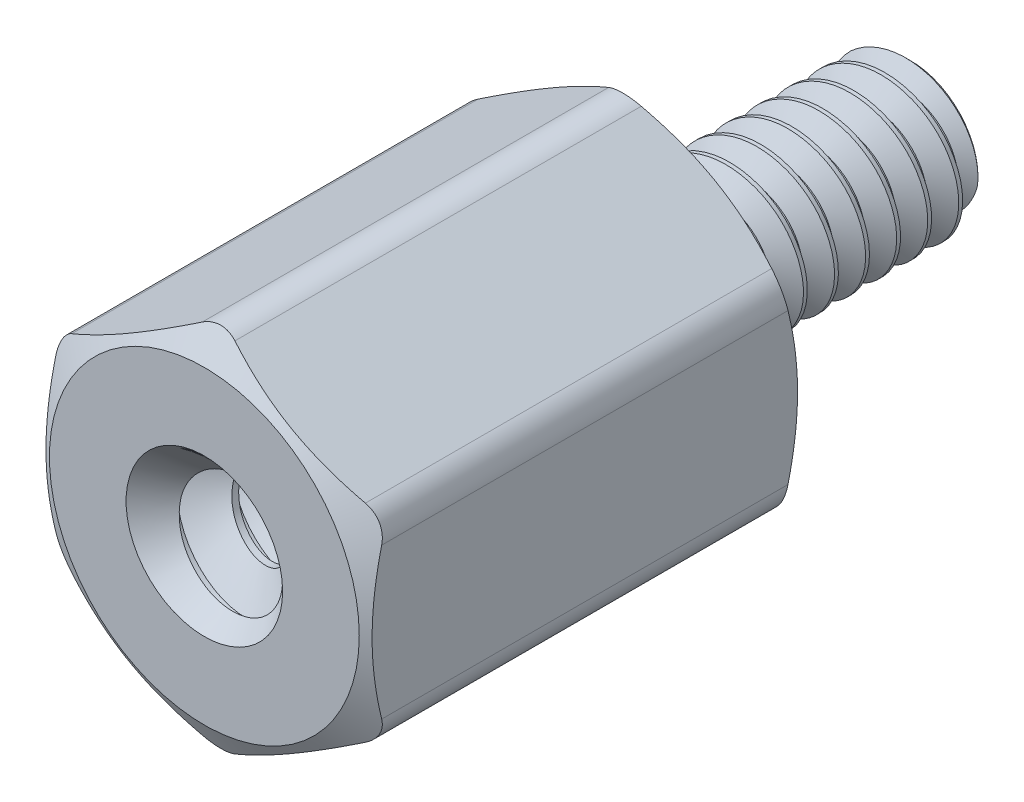
SolidWorks part; units mm, degrees
material "Alloy Steel"
ref_plane "Front Plane" through (0, 0, 0) normal (0, 0, 1) x (1, 0, 0)
ref_plane "Top Plane" through (0, 0, 0) normal (0, 1, 0) x (1, 0, 0)
ref_plane "Right Plane" through (0, 0, 0) normal (1, 0, 0) x (0, 0, -1)
sketch "Sketch1" plane through (0, 0, 0) normal (0, 0, 1) x (1, 0, 0)
  line L1 (2.3813, 1.3748) -> (0, 2.7496)
  line L2 (0, 2.7496) -> (-2.3812, 1.3748)
  line L3 (-2.3812, 1.3748) -> (-2.3812, -1.3748)
  line L4 (-2.3812, -1.3748) -> (0, -2.7496)
  line L5 (0, -2.7496) -> (2.3813, -1.3748)
  line L6 (2.3813, -1.3748) -> (2.3813, 1.3748)
  circle A0 centre (0, 0) radius 2.3812 construction
  point P10 (0, -2.3812)
  dimension "Hex Size" = 4.7625
sketch "Sketch2" plane through (0, 0, 0) normal (1, 0, 0) x (0, 0, -1)
  line L0 (3.9688, 0) -> (-6.35, 0) construction
  line L2 (0, 1.0922) -> (0, -1.0922) construction
  line L3 (-1.5748, 1.0922) -> (-1.5748, -1.0922) construction
  line L4 (-7.0941, 1.1781) -> (-6.6973, 0.4907) construction
  line L5 (-6.6973, 0.4907) -> (-6.3004, 1.1781) construction
  line L6 (-6.3004, 1.1781) -> (-7.0941, 1.1781) construction
  line L7 (-7.0445, 1.0922) -> (-6.35, 1.0922) construction
  line L8 (-6.7469, 0.5766) -> (-6.6477, 0.5766) construction
  line L9 (-6.6973, 0.5766) -> (-6.6973, 0.4907) construction
  line L10 (-6.6973, 1.0922) -> (-6.6973, 1.1781) construction
  line L11 (3.9404, 1.1413) -> (4.394, 1.1413) construction
  line L12 (4.394, 1.1413) -> (4.1672, 0.7485) construction
  line L13 (4.1672, 0.7485) -> (3.9404, 1.1413) construction
  line L14 (3.9688, 1.0922) -> (4.3656, 1.0922) construction
  line L15 (4.1388, 0.7976) -> (4.1955, 0.7976) construction
  line L16 (4.1672, 0.7976) -> (4.1672, 0.7485) construction
  line L17 (4.1672, 1.0922) -> (4.1672, 1.1413) construction
  line L18 (0, 2.7496) -> (-6.35, 2.7496) construction
  point P6 (0, 0)
  point P9 (-1.5748, 0)
  dimension "Length" = 6.35
sketch "Sketch3" plane through (0, 0, 0) normal (1, 0, 0) x (0, 0, -1)
  line L0 (-1.5748, 0) -> (3.9688, 0)
  line L1 (-1.5748, 1.0922) -> (-1.5748, -1.0922) construction
  line L2 (3.9688, 0) -> (3.9688, 0.9788)
  line L3 (3.9688, 0.9788) -> (3.8554, 1.0922)
  line L4 (3.8554, 1.0922) -> (0.6463, 1.0922)
  line L5 (0.6463, 1.0922) -> (0.4763, 0.7976)
  line L6 (-1.5748, 0) -> (-1.5748, 0.9788)
  line L7 (-1.5748, 0.9788) -> (-1.6882, 1.0922)
  line L8 (-1.6882, 1.0922) -> (-6.2366, 1.0922)
  line L9 (-6.2366, 1.0922) -> (-6.35, 1.2056)
  line L10 (3.8554, 0) -> (3.8554, -1.0922) construction
  line L11 (-6.35, 1.2056) -> (-6.35, 2.3812)
  line L12 (-6.35, 2.3812) -> (0, 2.3812)
  line L14 (0.4763, 0.7976) -> (0.1134, 0.7976)
  line L15 (0, 0.911) -> (0, 2.3812)
  arc A0 (0, 0.911) -> (0.1134, 0.7976) centre (0.1134, 0.911) ccw
  point P5 (-6.35, -2.3812)
  point P8 (-4.3656, -1.0922)
  point P9 (2.8348, -1.0922)
  point P27 (0, 0.7976)
  dimension "D4" = 0.1134
  dimension "D2" = 0.1134
  dimension "D1" = 45
  dimension "D6" = 1.1339
  dimension "D7" = 60
  dimension "D3" = 1.9844
  dimension "D5" = 0.4762
revolve "Revolve1" add sketch "Sketch3" angle 360 about L0 region at (0, 1.2337, 1.3349)
sketch "Sketch4" plane through (0, 0, 6.35) normal (0, 0, 1) x (1, 0, 0)
  line L0 (0, 2.3812) -> (0, 1.0922) construction
  line L1 (-2.3812, 1.3748) -> (-2.3812, -1.3748)
  line L2 (-2.3812, -1.3748) -> (0, -2.7496)
  line L3 (0, -2.7496) -> (2.3812, -1.3748)
  line L4 (2.3812, -1.3748) -> (2.3812, 1.3748)
  line L5 (2.3812, 1.3748) -> (0, 2.7496)
  line L6 (0, 2.7496) -> (-2.3812, 1.3748)
  circle A0 centre (0, 0) radius 2.3812 construction
  circle A1 centre (0, 0) radius 1.7367
  circle A2 centre (0, 0) radius 2.3812 construction
  point P16 (0, 1.7367)
extrude "Boss-Extrude1" add sketch "Sketch4" against normal up to surface (6.35 mm away) up to face at (0, 2.3812, 0)
sketch "Sketch5" plane through (0, 0, 6.35) normal (0, 0, 1) x (1, 0, 0)
  line L0 (-0.6265, 0.8947) -> (0.6265, -0.8947) construction
  line L1 (0, 1.0922) -> (0, -1.0922) construction
  line L3 (0, -5.8871) -> (0, 5.8871) construction
  circle A0 centre (0, 0) radius 2.2622
  point P11 (0.6265, -0.8947)
  dimension "D1" = 4.5244
  dimension "D2" = 35
extrude "Cut-Extrude1" cut sketch "Sketch5" against normal through all draft 60 flip side to cut
sketch "Sketch6" plane through (0, 0, 0) normal (0, 0, -1) x (-1, 0, 0)
  circle A0 centre (0, 0) radius 2.2622
  circle A1 centre (0, 0) radius 2.2622 construction
extrude "Cut-Extrude2" cut sketch "Sketch6" against normal through all draft 60 flip side to cut
fillet "Fillet1" radius 0.4763 6 edges at (0, 2.7496, 3.175) (-2.3812, -1.3748, 3.175) (0, -2.7496, 3.175) (2.3812, -1.3748, 3.175) (2.3812, 1.3748, 3.175) (-2.3812, 1.3748, 3.175)
sketch "Drawing1" plane through (0, 0, 0) normal (1, 0, 0) x (0, 0, -1)
  line L0 (-6.35, 1.0922) -> (-1.5748, 1.0922) construction
  line L1 (-1.5748, 1.0922) -> (-1.5748, -1.0922) construction
  line L2 (-1.5748, -1.0922) -> (-6.35, -1.0922) construction
sketch "Sketch7" plane through (0, 0, 0) normal (-1, 0, 0) x (0, 0, 1)
  line L0 (-4.1388, 0.7976) -> (-4.1955, 0.7976)
  line L1 (-4.1955, 0.7976) -> (-4.3798, 1.1168)
  line L2 (-4.394, 1.1413) -> (-4.1672, 0.7485) construction
  line L3 (-4.3798, 1.1168) -> (-3.9546, 1.1168)
  line L4 (-4.1672, 0.7485) -> (-3.9404, 1.1413) construction
  line L5 (-3.9546, 1.1168) -> (-4.1388, 0.7976)
  line L6 (-4.1672, 1.0922) -> (-4.1672, 1.1413) construction
  point P12 (-4.1672, 1.1168)
sketch "Sketch8" plane through (0, 0, -3.9688) normal (0, 0, -1) x (-1, 0, 0)
  circle A0 centre (0, 0) radius 1.0922
curve "Helix/Spiral1" pitch 0.4536 height 3.8497 radius 1.0922 centre (0, 0, -3.9688) axis (0, 0, 1) start towards (0, 1, 0)
sweep "Cut-Sweep1" cut profiles "Sketch7" path "Helix/Spiral1" align with end faces yes
sketch "Sketch9" plane through (0, 0, 1.5748) normal (0, 0, 1) x (1, 0, 0)
  circle A0 centre (0, 0) radius 1.2056
extrude "Boss-Extrude2" add sketch "Sketch9" along normal up to surface (4.7752 mm away) up to face at (0, 1.2056, 6.35)
sketch "Sketch10" plane through (0, 0, 0) normal (1, 0, 0) x (0, 0, -1)
  line L0 (3.9688, 0) -> (-6.35, 0) construction
  line L1 (-1.5748, 1.0922) -> (-6.35, 1.0922)
  line L2 (-1.5748, 1.0922) -> (-1.5748, 0)
  line L3 (-1.5748, 0) -> (-6.35, 0)
  line L4 (-6.35, 1.0922) -> (-6.35, 0)
revolve "Revolve2" add sketch "Sketch10" angle 360 about L0
sketch "Sketch11" plane through (0, 0, 6.35) normal (0, 0, 1) x (1, 0, 0)
  circle A0 centre (0, 0) radius 1.0922
  circle A1 centre (0, 0) radius 1.0922 construction
sketch "Sketch12" plane through (0, 0, 0) normal (1, 0, 0) x (0, 0, -1)
  line L0 (-6.7469, 0.5766) -> (-6.6477, 0.5766)
  line L1 (-6.6477, 0.5766) -> (-6.3252, 1.1352)
  line L2 (-6.6973, 0.4907) -> (-6.3004, 1.1781) construction
  line L3 (-6.3252, 1.1352) -> (-7.0693, 1.1352)
  line L4 (-7.0941, 1.1781) -> (-6.6973, 0.4907) construction
  line L5 (-7.0693, 1.1352) -> (-6.7469, 0.5766)
  line L6 (-6.6973, 1.0922) -> (-6.6973, 1.1781) construction
  point P12 (-6.6973, 1.1352)
curve "Helix/Spiral2" pitch 0.7937 height 5.5689 radius 1.0922 centre (0, 0, 6.35) axis (0, 0, -1) start towards (0, 1, 0)
sweep "Cut-Sweep2" cut profiles "Sketch12" path "Helix/Spiral2" align with end faces yes
combine bodies "Combine1" operation type subtract main body 113 bodies to subtract 114
sketch "Sketch13" plane through (0, 0, 6.35) normal (0, 0, 1) x (1, 0, 0)
  circle A0 centre (0, 0) radius 1.143
  dimension "D1" = 0.0508
extrude "Cut-Extrude3" cut sketch "Sketch13" against normal through all draft 45
equation "\"Thread Pitch (B)/8@Sketch2\"=\"Thread Pitch (B)@Sketch2\"/8"
equation "\"Thread Pitch (A)/8@Sketch2\"=\"Thread Pitch (A)@Sketch2\"/8"
equation "\"D1@Sketch5\" = \"Hex Size@Sketch1\" * .95"
equation "\"D1@Fillet1\" = \"Hex Size@Sketch1\" * .1"
equation "\"D2@Sketch3\" = \"Thread Pitch (A)@Sketch2\" * .25"
equation "\"D4@Sketch3\" = \"D2@Sketch3\""
equation "\"D6@Sketch3\" = \"Thread Pitch (A)@Sketch2\" * 2.5"
equation "\"D3@Helix/Spiral1\" = \"Thread Length (A)@Sketch2\" - \"D5@Sketch3\" * .25"
equation "\"D4@Helix/Spiral1\" = \"Thread Pitch (A)@Sketch2\""
equation "\"D3@Sketch3\" = \"Thread Pitch (B)@Sketch2\" * 2.5"
equation "\"D5@Sketch3\" = \"Thread Length (A)@Sketch2\" * .12"
equation "\"D3@Helix/Spiral2\" = \"Minimum Thread Length (B)@Sketch2\" + \"Thread Pitch (B)@Sketch2\""
equation "\"D4@Helix/Spiral2\" = \"Thread Pitch (B)@Sketch2\""
